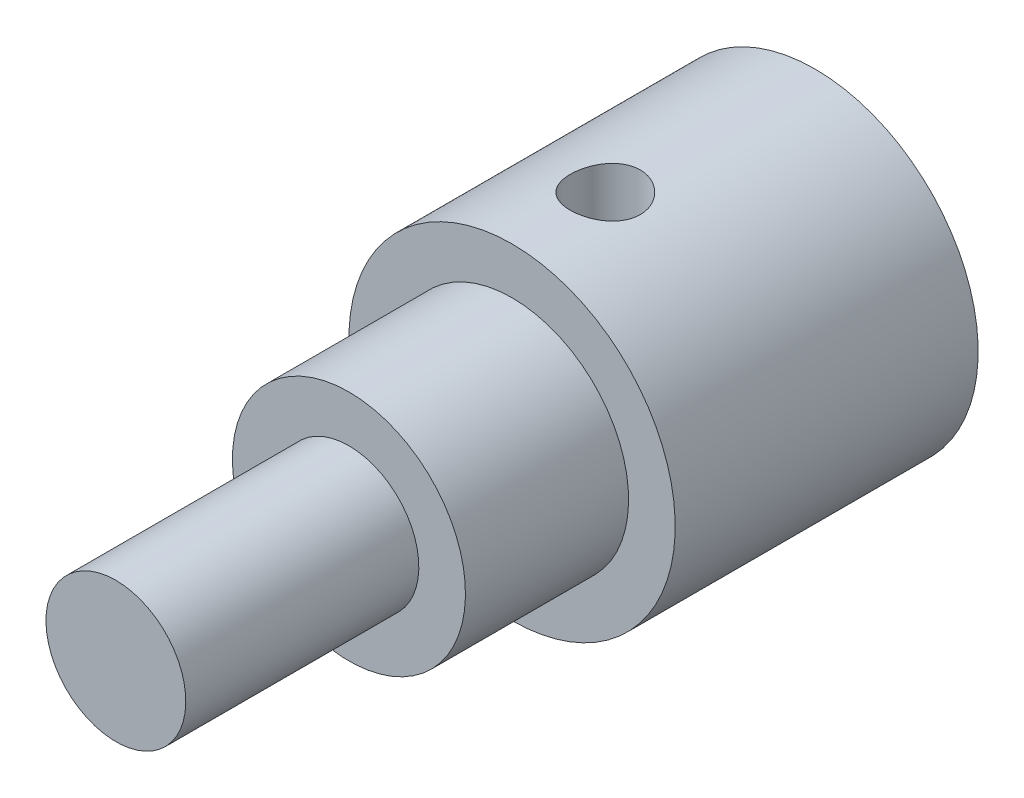
SolidWorks part; units mm, degrees
material "1060 Alloy"
ref_plane "Front Plane" through (0, 0, 0) normal (0, 0, 1) x (1, 0, 0)
ref_plane "Top Plane" through (0, 0, 0) normal (0, 1, 0) x (1, 0, 0)
ref_plane "Right Plane" through (0, 0, 0) normal (1, 0, 0) x (0, 0, -1)
sketch "Sketch1" plane through (0, 0, 0) normal (1, 0, 0) x (0, 0, -1)
  line L0 (0, 0) -> (0, 3)
  line L1 (0, 3) -> (10, 3)
  line L2 (10, 3) -> (10, 5)
  line L3 (10, 5) -> (17, 5)
  line L4 (17, 5) -> (17, 7)
  line L5 (17, 7) -> (30, 7)
  line L6 (17.5772, 0) -> (19.5, 3.2)
  line L7 (17.5772, 0) -> (0, 0)
  line L8 (19.5, 3.2) -> (30, 3.2)
  line L9 (30, 3.2) -> (30, 7)
  dimension "D1" = 3
  dimension "D2" = 10
  dimension "D3" = 7
  dimension "D4" = 5
  dimension "D5" = 13
  dimension "D6" = 7
  dimension "D7" = 3.2
  dimension "D8" = 2.5
  dimension "D9" = 121
revolve "Revolve1" add sketch "Sketch1" angle 360 about L7
sketch "Sketch2" plane through (0, 0, 0) normal (0, 1, 0) x (1, 0, 0)
  line L1 (-7, 17) -> (7, 17) construction
  circle A0 centre (0, 21) radius 1.5
  dimension "D2" = 3
  dimension "D1" = 4
extrude "Cut-Extrude1" cut sketch "Sketch2" against normal up to next and the other way up to next
